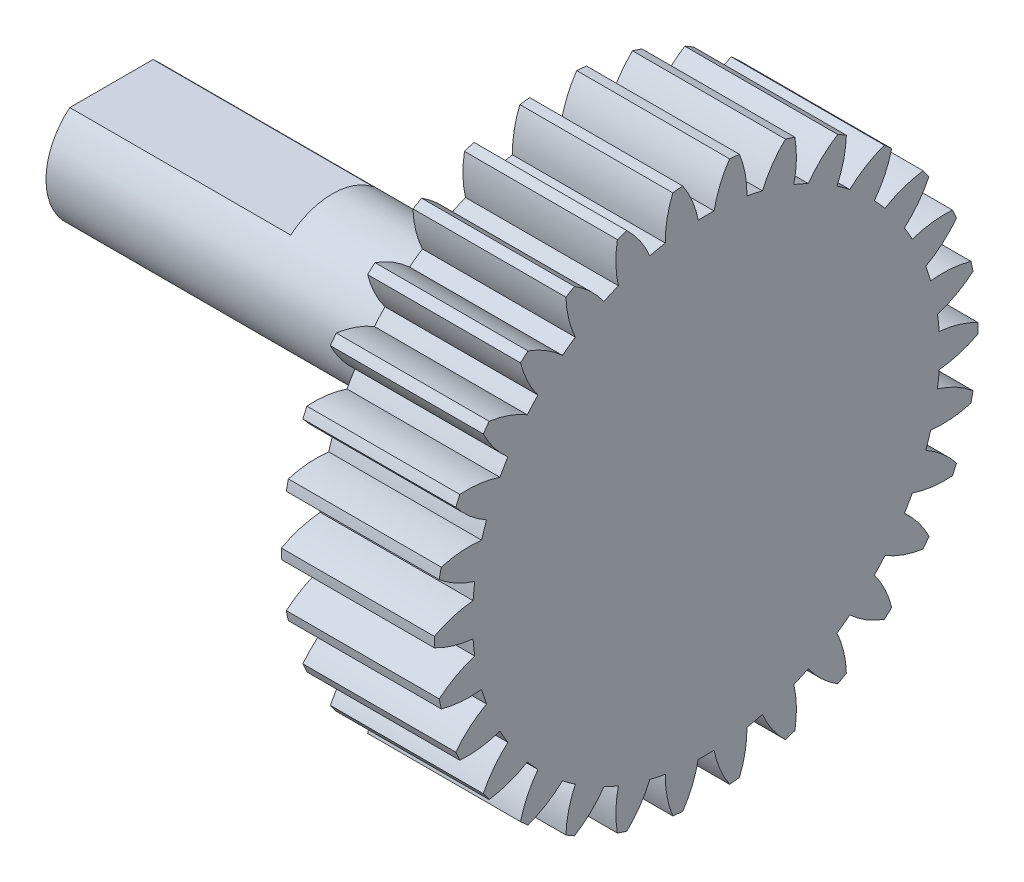
SolidWorks part; units mm, degrees
ref_plane "Plane1" through (0, 0, 0) normal (0, 0, 1) x (1, 0, 0)
ref_plane "Plane2" through (0, 0, 0) normal (0, 1, 0) x (1, 0, 0)
ref_plane "Plane3" through (0, 0, 0) normal (1, 0, 0) x (0, 0, -1)
sketch "HoldingSke" plane through (0, 0, 0) normal (0, 1, 0) x (1, 0, 0)
  line L0 (0, 0) -> (0.866, -0.5)
  line L1 (-15, 0) -> (100, 0) construction
  line L2 (0, 0) -> (-2.1039, 2.3779)
  line L3 (0, 0) -> (-11.863, 4.5341)
  line L4 (0, 0) -> (7.479, 4.318)
  line L5 (0, 0) -> (-46.8476, -17.4728)
  line L6 (0, 0) -> (-7.4607, -5.0337)
  line L7 (-2.1039, 2.3779) -> (8.6586, 51.2059)
  line L8 (-76.2, 54.61) -> (-74.8, 54.61)
  line L9 (-71.009, 38.7566) -> (-53.1078, 45.2721)
  line L10 (-76.2, 71.12) -> (104.1128, 71.12)
  line L11 (0, 0) -> (-9, 0)
  line L12 (-76.2, 101.6) -> (-76.162, 101.6)
  line L13 (24.9733, 27.94) -> (52.9518, 28.4284)
  line L14 (24.9733, 27.94) -> (24.9743, 27.94)
  line L15 (24.9733, 27.94) -> (100.4006, 29.5858)
  line L16 (-63.627, -1) -> (-12.827, -1)
  circle A0 centre (0, 0) radius 4
  circle A1 centre (0, 0) radius 13.749
  circle A2 centre (0, 0) radius 37.5
  circle A3 centre (0, 0) radius 4
  dimension "MHD" = 27.498
  dimension "Hub_dia" = 75
  dimension "Bore" = 8
  dimension "MBD" = 8
  dimension "Num_teeth" = 30
  dimension "Pitch" = 1
  dimension "Overall_len" = 50
  dimension "Show_teeth" = 30
  dimension "Thickness" = 9
  dimension "OAL" = 50.0001
  dimension "T_dim" = 1.4
  dimension "Ap" = 20
  dimension "H" = 19.05
  dimension "Pitch_radius" = 180.3128
  dimension "Width" = 9
  dimension "Backlash" = 0.038
  dimension "Addendum_fac" = 1
  dimension "Dedendum_fac" = 1.25
  dimension "Clearance_fac" = 0.25
  dimension "Dedendum_add" = 0.001
  dimension "Module" = 1
sketch "BasProSke" plane through (0, 0, 0) normal (0, 1, 0) x (1, 0, 0)
  line L0 (-10, 0) -> (60, 0) construction
  line L1 (0, 0) -> (0, 16)
  line L2 (0, 0) -> (9, 0)
  line L3 (9, 0) -> (9, 16)
  line L4 (9, 16) -> (0, 16)
  dimension "Thickness" = 9
  dimension "Diameter" = 32
revolve "Base-Revolve" add sketch "BasProSke" angle 360 about L0
sketch "TooCutSke" plane through (0, 0, 0) normal (1, 0, 0) x (0, 0, -1)
  line L1 (0, 0) -> (0, 107) construction
  line L2 (0, 0) -> (-0.8515, 14.9758) construction
  line L3 (0, 0) -> (-3.1323, 29.8014) construction
  line L4 (-0.8515, 14.9758) -> (-1.5661, 14.9007) construction
  arc A0 (0.4664, 13.7411) -> (-0.4664, 13.7411) centre (0, 0) ccw
  arc A1 (1.3975, 15.9644) -> (-1.3975, 15.9644) centre (0, 0) ccw
  circle A2 centre (0, 0) radius 15 construction
  circle A3 centre (0, 0) radius 14.0954 construction
  arc A4 (-0.4664, 13.7411) -> (-1.3975, 15.9644) centre (-6.3534, 12.5823) ccw
  arc A5 (1.3975, 15.9644) -> (0.4664, 13.7411) centre (6.3534, 12.5823) ccw
  dimension "Root_dia" = 27.498
  dimension "Overcut_dia" = 32.0508
  dimension "Pitch_dia" = 30
  dimension "Base_dia" = 28.1908
  dimension "Flank_rad" = 6
  dimension "Half_ang" = 6
  dimension "Half_CT" = 0.7185
extrude "ToothCut" cut sketch "TooCutSke" along normal through all
fillet "Breaks" [suppressed] radius 0.02 tangent propagation no
fillet "RootFillets" [suppressed] radius 0.251
pattern_circular "TeethCuts" count 30 every 12 about axis through (-10, 0, 0) along (1, 0, 0) of "ToothCut", "RootFillets", "Breaks"
sketch "HubNeaOneSke" plane through (0, 0, 0) normal (-1, 0, 0) x (0, 0, 1)
  circle A0 centre (0, 0) radius 13.749
  dimension "Diameter" = 27.498
extrude "HubNearOne" [suppressed] add sketch "HubNeaOneSke" along normal blind 41.0001
sketch "HubNeaBotSke" plane through (0, 0, 0) normal (-1, 0, 0) x (0, 0, 1)
  circle A0 centre (0, 0) radius 13.749
  dimension "Diameter" = 27.498
extrude "HubNearBoth" [suppressed] add sketch "HubNeaBotSke" along normal blind 20.5
ref_plane "FarPln" through (9, 0, 0) normal (1, 0, 0) x (0, 0, -1)
sketch "HubFarSke" plane through (9, 0, 0) normal (1, 0, 0) x (0, 0, -1)
  circle A0 centre (0, 0) radius 13.749
  dimension "Diameter" = 27.498
extrude "HubFar" [suppressed] add sketch "HubFarSke" along normal blind 20.5
sketch "BorSke" plane through (0, 0, 0) normal (1, 0, 0) x (0, 0, -1)
  circle A0 centre (0, 0) radius 4
  dimension "Diameter" = 8
extrude "Bore" cut sketch "BorSke" along normal mid plane 100.0001
sketch "KeySke" plane through (0, 0, 0) normal (1, 0, 0) x (0, 0, -1)
  line L0 (-1.5, 0) -> (-1.5, 5.4)
  line L1 (-1.5, 5.4) -> (1.5, 5.4)
  line L2 (1.5, 5.4) -> (1.5, 0)
  line L3 (0, 0) -> (0, 34) construction
  line L4 (-1.5, 0) -> (1.5, 0)
  dimension "Offset" = 5.4
  dimension "Width" = 3
extrude "Keyway" [suppressed] cut sketch "KeySke" along normal mid plane 100.0001
pattern_circular "Keyway2" [suppressed] count 2 every 90 about axis through (-10, 0, 0) along (1, 0, 0) reverse direction yes
ref_plane "Plane4" through (0, 11.3909, 7.6995) normal (0, 0.56, -0.8285) x (-1, 0, 0)
sketch "Sketch2" plane through (0, 0, 0) normal (-1, 0, 0) x (0, 0, 1)
  line L0 (-2.45, 2.9698) -> (2.45, 2.9698)
  circle A0 centre (0, 0) radius 3.85
  circle A1 centre (0, 0) radius 4.5
  point P4 (0, 0)
  point P5 (0, 0)
  point P6 (0, 0)
  point P9 (0, 0)
  dimension "D1" = 4.9
  dimension "D2" = 7.7
  dimension "D3" = 9
extrude "Boss-Extrude3" add sketch "Sketch2" along normal blind 26 and the other way blind 9 separate body contours L0 A0 region at (0, -0.2248, 0)
extrude "Boss-Extrude4" add sketch "Sketch2<5>" along normal blind 13 and the other way blind 9 contours L0 A0 region at (0, 3.3256, 0)
sketch "Sketch2<5>" plane through (0, 0, 0) normal (-1, 0, 0) x (0, 0, 1) same geometry as "Sketch2"
extrude "Boss-Extrude5" add sketch "Sketch2<6>" along normal blind 1 and the other way blind 9 contours A1 A0 region at (0, 0, -4.3727)
sketch "Sketch2<6>" plane through (0, 0, 0) normal (-1, 0, 0) x (0, 0, 1) same geometry as "Sketch2"
equation "' \"Module@HoldingSke\" = 6.35"
equation "' \"Num_teeth@HoldingSke\" = 12"
equation "' \"Ap@HoldingSke\" =  20"
equation "' \"Ap@HoldingSke\" = 20"
equation "' \"Width@HoldingSke\" = 0.5 * 25.4"
equation "' \"Hub_dia@HoldingSke\"= 1 * 25.4"
equation "' \"Hub_dia@HoldingSke\" = 1 * 25.4"
equation "' \"Overall_len@HoldingSke\" = 1.0 * 25.4"
equation "' \"Bore@HoldingSke\" = 0.75 * 25.4"
equation "' \"T_dim@HoldingSke\" = 0.1 * 25.4"
equation "' \"Width@KeySke\" = 0.25 * 25.4"
equation "' \"Show_teeth@HoldingSke\" = 13"
equation "' \"Backlash@HoldingSke\" = 0.009 * 25.4"
equation "' \"Addendum_fac@HoldingSke\" = 1.0"
equation "' \"Dedendum_fac@HoldingSke\" = 1.25"
equation "' \"Dedendum_add@HoldingSke\" = 0.00005 * 25.4"
equation "' \"Clearance_fac@HoldingSke\" = 0.25"
equation "\"Pitch@HoldingSke\" = 1 / \"Module@HoldingSke\""
equation "\"Overcut_dia@TooCutSke\" = (\"Num_teeth@HoldingSke\" + 2 * \"Addendum_fac@HoldingSke\") / \"Pitch@HoldingSke\" + 0.002 * 25.4"
equation "\"Pitch_dia@TooCutSke\" = \"Num_teeth@HoldingSke\" / \"Pitch@HoldingSke\""
equation "\"Base_dia@TooCutSke\" = \"Num_teeth@HoldingSke\" / \"Pitch@HoldingSke\" * cos((\"Ap@HoldingSke\"  * 3.14159265 / 180))"
equation "\"Root_dia@TooCutSke\" = (\"Num_teeth@HoldingSke\" + 2) / \"Pitch@HoldingSke\" - 2 * (\"Addendum_fac@HoldingSke\" + \"Dedendum_fac@HoldingSke\") / \"Pitch@HoldingSke\" - \"Dedendum_add@HoldingSke\" * 2"
equation "\"Half_ang@TooCutSke\" = 180 / \"Num_teeth@HoldingSke\""
equation "\"Half_CT@TooCutSke\" = \"Num_teeth@HoldingSke\" / \"Pitch@HoldingSke\" * sin((3.14159265 / 2 / \"Num_teeth@HoldingSke\")) / 2 - 7 * \"Backlash@HoldingSke\" / 4"
equation "\"Flank_rad@TooCutSke\" = \"Num_teeth@HoldingSke\" / \"Pitch@HoldingSke\" / 5"
equation "\"Radius@RootFillets\" = \"Clearance_fac@HoldingSke\" / \"Pitch@HoldingSke\" + \"Dedendum_add@HoldingSke\""
equation "\"Break_rad@Breaks\" = 0.02 / \"Pitch@HoldingSke\""
equation "\"Thickness@HoldingSke\" = \"Width@HoldingSke\""
equation "\"OAL@HoldingSke\" = \"Thickness@HoldingSke\""
equation "\"MHD@HoldingSke\" = (\"Num_teeth@HoldingSke\" + 2) / \"Pitch@HoldingSke\" - 2 * (\"Addendum_fac@HoldingSke\" + \"Dedendum_fac@HoldingSke\")  / \"Pitch@HoldingSke\" - \"Dedendum_add@HoldingSke\" * 2"
equation "\"MBD@HoldingSke\" = (\"Num_teeth@HoldingSke\" + 2) / \"Pitch@HoldingSke\" - 2 * (\"Addendum_fac@HoldingSke\" + \"Dedendum_fac@HoldingSke\")  / \"Pitch@HoldingSke\" - \"Dedendum_add@HoldingSke\" * 2 - 0.002 * 25.4"
equation "\"MHD@HoldingSke\" = ((sgn( \"MHD@HoldingSke\" - \"Hub_dia@HoldingSke\" )-1)*( \"MHD@HoldingSke\" - \"Hub_dia@HoldingSke\" ))/-2+ \"Hub_dia@HoldingSke\""
equation "\"MBD@HoldingSke\" = ((sgn( \"MBD@HoldingSke\" - \"Bore@HoldingSke\" )-1)*( \"MBD@HoldingSke\" - \"Bore@HoldingSke\" ))/-2+ \"Bore@HoldingSke\""
equation "\"OAL@HoldingSke\" = ((sgn( \"OAL@HoldingSke\" - \"Overall_len@HoldingSke\" )+1)*( \"OAL@HoldingSke\" - \"Overall_len@HoldingSke\" ))/2 + \"Overall_len@HoldingSke\" + 0.000002 * 25.4"
equation "\"Num_teeth@TeethCuts\" = int( \"Show_teeth@HoldingSke\" ) + 1"
equation "\"Num_teeth@TeethCuts\" = ((sgn( \"Num_teeth@TeethCuts\" - \"Num_teeth@HoldingSke\" )-1)*( \"Num_teeth@TeethCuts\" - \"Num_teeth@HoldingSke\" ))/-2+ \"Num_teeth@HoldingSke\""
equation "\"Num_teeth@TeethCuts\" = ((sgn( \"Num_teeth@TeethCuts\" - 2.0)+1)*( \"Num_teeth@TeethCuts\" - 2.0))/2 +2.0"
equation "\"Angle@TeethCuts\" = 360.0 / \"Num_teeth@HoldingSke\""
equation "\"Diameter@BasProSke\" = (\"Num_teeth@HoldingSke\" + 2 * \"Addendum_fac@HoldingSke\") / \"Pitch@HoldingSke\""
equation "\"Thickness@BasProSke\"  = \"Thickness@HoldingSke\""
equation "' \"Fillet_rad@BasProSke\" =  \"Thickness@HoldingSke\" * 0.05"
equation "' \"Fillet_rad@BasProSke\" = \"Thickness@HoldingSke\" * 0.05"
equation "\"MHD@HoldingSke\" = ((sgn( \"MHD@HoldingSke\" - \"Root_dia@TooCutSke\" )-1)*( \"MHD@HoldingSke\" - \"Root_dia@TooCutSke\" ))/-2+ \"Root_dia@TooCutSke\""
equation "\"Diameter@HubNeaOneSke\" = \"MHD@HoldingSke\""
equation "\"Length@HubNearOne\" = \"OAL@HoldingSke\" - \"Thickness@BasProSke\""
equation "\"Diameter@HubNeaBotSke\" = \"MHD@HoldingSke\""
equation "\"Length@HubNearBoth\" = ( \"OAL@HoldingSke\" - \"Thickness@BasProSke\" ) / 2.0"
equation "\"Thickness@FarPln\" = \"Thickness@BasProSke\""
equation "\"Diameter@HubFarSke\" = \"MHD@HoldingSke\""
equation "\"Length@HubFar\" = ( \"OAL@HoldingSke\" - \"Thickness@BasProSke\" ) / 2.0"
equation "\"Diameter@BorSke\" = \"MBD@HoldingSke\""
equation "\"D1@Bore\" = \"OAL@HoldingSke\" * 2.0"
equation "\"D1@Keyway\" = \"OAL@HoldingSke\" * 2.0"
equation "\"Offset@KeySke\" = \"T_dim@HoldingSke\" + \"MBD@HoldingSke\" / 2.0"
